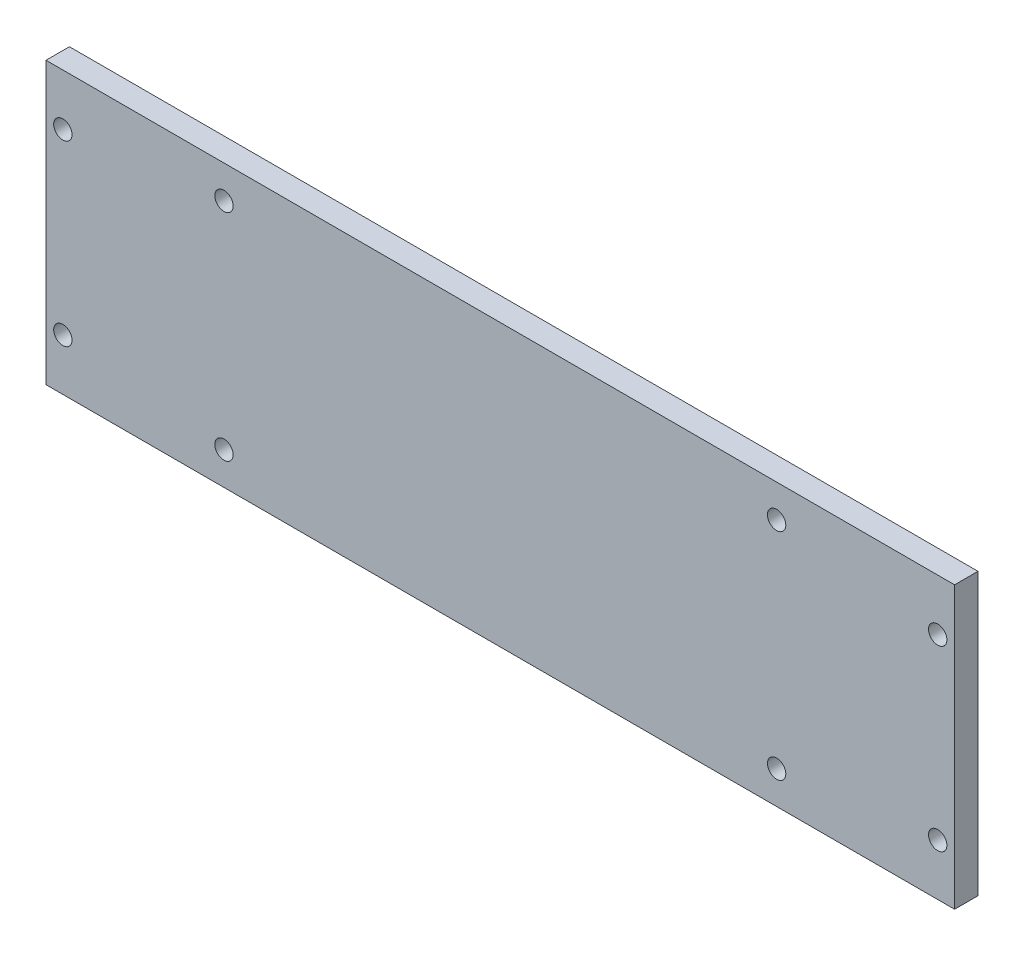
SolidWorks part; units mm, degrees
material "6061-T6 (SS)"
ref_plane "Front Plane" through (0, 0, 0) normal (0, 0, 1) x (1, 0, 0)
ref_plane "Top Plane" through (0, 0, 0) normal (0, 1, 0) x (1, 0, 0)
ref_plane "Right Plane" through (0, 0, 0) normal (1, 0, 0) x (0, 0, -1)
sketch "Sketch1" plane through (0, 0, 0) normal (0, 0, 1) x (1, 0, 0)
  line L1 (-123.19, 38.1) -> (123.19, 38.1)
  line L2 (-123.19, 38.1) -> (-123.19, -38.1)
  line L3 (-123.19, -38.1) -> (123.19, -38.1)
  line L4 (123.19, 38.1) -> (123.19, -38.1)
  line L5 (-123.19, 38.1) -> (123.19, -38.1) construction
  line L6 (-123.19, -38.1) -> (123.19, 38.1) construction
  point P0 (0, 0)
  dimension "D1" = 76.2
  dimension "D2" = 246.38
extrude "Boss-Extrude1" add sketch "Sketch1" along normal blind 6.35
sketch "Sketch2" plane through (0, 0, 6.35) normal (0, 0, 1) x (1, 0, 0)
  line L0 (123.19, -38.1) -> (123.19, 38.1) construction
  line L1 (-74.93, 29.21) -> (74.93, 29.21) construction
  line L2 (-74.93, 29.21) -> (-74.93, -29.21) construction
  line L3 (-74.93, -29.21) -> (74.93, -29.21) construction
  line L4 (74.93, 29.21) -> (74.93, -29.21) construction
  line L5 (-74.93, 29.21) -> (74.93, -29.21) construction
  line L6 (-74.93, -29.21) -> (74.93, 29.21) construction
  line L7 (118.618, -24.13) -> (-118.618, -24.13) construction
  line L8 (118.618, -24.13) -> (118.618, 24.13) construction
  line L9 (118.618, 24.13) -> (-118.618, 24.13) construction
  line L10 (-118.618, -24.13) -> (-118.618, 24.13) construction
  line L11 (118.618, -24.13) -> (-118.618, 24.13) construction
  line L12 (118.618, 24.13) -> (-118.618, -24.13) construction
  point P0 (0, 0)
  point P6 (0, 0)
  dimension "D1" = 149.86
  dimension "D2" = 58.42
  dimension "D3" = 4.572
  dimension "D4" = 48.26
hole_wizard "#10 Clearance Hole1" positions "Sketch3" profile "Sketch4" hole size "#10" standard "ANSI Inch" end condition through all
sketch "Sketch3" plane through (0, 0, 6.35) normal (0, 0, 1) x (1, 0, 0)
  point P0 (-74.93, 29.21)
  point P3 (-74.93, -29.21)
  point P6 (74.93, 29.21)
  point P9 (74.93, -29.21)
  point P12 (-118.618, 24.13)
  point P15 (-118.618, -24.13)
  point P18 (118.618, 24.13)
  point P21 (118.618, -24.13)
sketch "Sketch4" plane through (-74.93, 29.21, 6.35) normal (1, 0, 0) x (0, -1, 0)
  line L0 (0, 0) -> (0, 6.35)
  line L1 (0, 6.35) -> (2.4892, 6.35)
  line L2 (2.4892, 6.35) -> (2.4892, 0)
  line L5 (2.4892, 0) -> (0, 0)
  line L11 (0, -6.35) -> (0, 107.95) construction
  dimension "Thru Hole Dia." = 4.9784
  dimension "Thru Hole Depth" = 6.35
